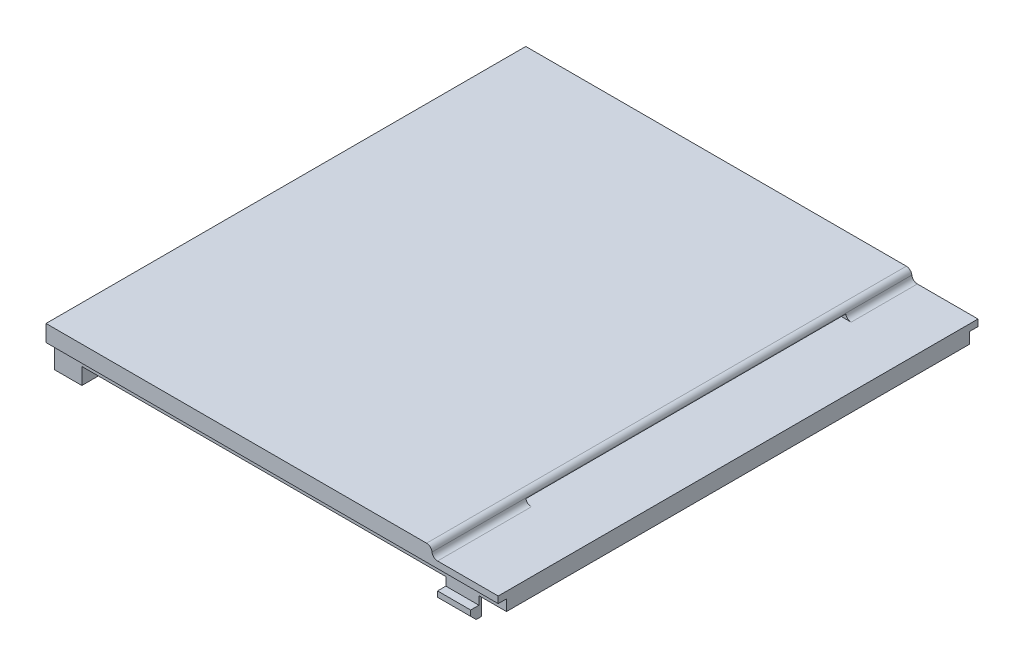
SolidWorks part; units mm, degrees
note: The reader was unsure of these and kept them because the rebuilt part matched: shared geometry of "Эскиз3<3>".
ref_plane "Front" through (0, 0, 0) normal (0, 0, 1) x (1, 0, 0)
ref_plane "Top" through (0, 0, 0) normal (0, 1, 0) x (1, 0, 0)
ref_plane "Right" through (0, 0, 0) normal (1, 0, 0) x (0, 0, -1)
sketch "Эскиз2" plane through (0, 0, 0) normal (1, 0, 0) x (0, 0, -1)
  line L0 (-42, -1.5) -> (-42, -3.5)
  line L1 (43.5, -1.5) -> (-43.5, -1.5)
  line L2 (43.5, -1.5) -> (43.5, 1.5)
  line L3 (43.5, 1.5) -> (-43.5, 1.5)
  line L4 (-43.5, -1.5) -> (-43.5, 1.5)
  line L5 (43.5, -1.5) -> (-43.5, 1.5) construction
  line L6 (43.5, 1.5) -> (-43.5, -1.5) construction
  line L7 (-42, -3.5) -> (-40, -3.5)
  line L8 (-40, -3.5) -> (-40, -1.5)
  line L9 (42, -1.5) -> (42, -3.5)
  line L10 (42, -3.5) -> (40, -3.5)
  line L11 (40, -3.5) -> (40, -1.5)
  line L12 (-40, -3.5) -> (40, -3.5)
  point P0 (0, 0)
  dimension "D1" = 3
  dimension "D2" = 87
  dimension "D3" = 2
  dimension "D4" = 2
  dimension "D5" = 2
  dimension "D6" = 2
  dimension "D7" = 84
  dimension "D8" = 42
extrude "Бобышка-Вытянуть1" add sketch "Эскиз2" along normal blind 82 contours L4 L1 L2 L3 | L7 L8 L1 L0 | L11 L10 L9 L1 | L8 L12 L11 L1
sketch "Эскиз3" plane through (0, 0, 0) normal (1, 0, 0) x (0, 0, -1)
  line L0 (-42, -6.5) -> (42, -6.5)
  line L1 (42, -6.5) -> (42, 1.5)
  line L2 (43.5, 1.5) -> (-43.5, 1.5) construction
  line L3 (42, 1.5) -> (-42, 1.5)
  line L4 (-42, 1.5) -> (-42, -6.5)
  line L6 (4.8, -4.65) -> (-4.8, -4.65)
  line L7 (4.8, -4.65) -> (4.8, -3.15)
  line L8 (4.8, -3.15) -> (-4.8, -3.15)
  line L9 (-4.8, -4.65) -> (-4.8, -3.15)
  line L10 (4.8, -4.65) -> (-4.8, -3.15) construction
  line L11 (4.8, -3.15) -> (-4.8, -4.65) construction
  line L12 (-25.2, -4.65) -> (-34.8, -4.65)
  line L13 (-25.2, -4.65) -> (-25.2, -3.15)
  line L14 (-25.2, -3.15) -> (-34.8, -3.15)
  line L15 (-34.8, -4.65) -> (-34.8, -3.15)
  line L16 (-25.2, -4.65) -> (-34.8, -3.15) construction
  line L17 (-25.2, -3.15) -> (-34.8, -4.65) construction
  line L18 (34.8, -4.65) -> (25.2, -4.65)
  line L19 (34.8, -4.65) -> (34.8, -3.15)
  line L20 (34.8, -3.15) -> (25.2, -3.15)
  line L21 (25.2, -4.65) -> (25.2, -3.15)
  line L22 (34.8, -4.65) -> (25.2, -3.15) construction
  line L23 (34.8, -3.15) -> (25.2, -4.65) construction
  point P4 (-30, -3.9)
  point P10 (0, -3.9)
  point P18 (30, -3.9)
  point P23 (0, 0)
  point P25 (0, 0)
  dimension "D1" = 8
  dimension "D2" = 30
  dimension "D3" = 30
  dimension "D4" = 1.5
  dimension "D5" = 9.6
  dimension "D6" = 9.6
  dimension "D7" = 9.6
  dimension "D8" = 1.5
  dimension "D9" = 1.5
  dimension "D10" = 3.9
extrude "Бобышка-Вытянуть2" add sketch "Эскиз3" along normal blind 5 contours L0 L1 L3 L4
extrude "Бобышка-Вытянуть3" add sketch "Эскиз3<3>" against normal blind 2 contours L21 L18 L19 L20 | L9 L6 L7 L8 | L15 L12 L13 L14
sketch "Эскиз3<3>" plane through (0, 0, 0) normal (1, 0, 0) x (0, 0, -1) same geometry as "Эскиз3"
sketch "Эскиз4" plane through (0, 0, 0) normal (1, 0, 0) x (0, 0, -1)
  line L1 (31.5, -0.3) -> (-26.5, -0.3)
  line L2 (31.5, -0.3) -> (31.5, 0.5)
  line L3 (31.5, 0.5) -> (-26.5, 0.5)
  line L4 (-26.5, -0.3) -> (-26.5, 0.5)
  line L5 (31.5, -0.3) -> (-26.5, 0.5) construction
  line L6 (31.5, 0.5) -> (-26.5, -0.3) construction
  point P0 (2.5, 0.1)
  dimension "D1" = 0.8
  dimension "D2" = 58
  dimension "D3" = 0.3
  dimension "D4" = 2.5
extrude "Вырез-Вытянуть1" cut sketch "Эскиз4" along normal through all
fillet "Скругление1" radius 1.2 1 edges at (0, -0.3, -2.5)
sketch "Эскиз5" plane through (0, 0, 0) normal (0, 1, 0) x (1, 0, 0)
  line L0 (0, 0) -> (70, 0)
  line L1 (70, 0) -> (70, 45.9648)
  line L2 (70, 45.9648) -> (87.6516, 45.9648)
  line L3 (87.6516, 45.9648) -> (87.6516, -47.5311)
  line L4 (87.6516, -47.5311) -> (70, -47.5311)
  line L5 (70, -47.5311) -> (70, 0)
  dimension "D1" = 70
extrude "Вырез-Вытянуть2" cut sketch "Эскиз5" along normal through all from surface at -0.3 contours L5 L4 L3 L2 L1 starting at face at (41.6, -0.3, -2.5)
sketch "Эскиз6" plane through (0, 0, 0) normal (1, 0, 0) x (0, 0, -1)
  line L0 (-42, -1.5) -> (-42, -3.5) construction
  line L1 (-42, -3.0496) -> (-42, -5)
  line L2 (-42, -5) -> (-43.5, -5)
  line L4 (-42, -7) -> (-41.5, -7)
  line L5 (-41.5, -7) -> (-41.5, -3.0496)
  line L6 (-42, -7) -> (-42.5, -7)
  line L7 (-42, -3.0496) -> (-41.5, -3.0496)
  line L8 (-42.5, -7) -> (-45.105, -4.395)
  line L9 (-43.5, -5) -> (-43.5, -6)
  dimension "D1" = 0.5
  dimension "D2" = 45
  dimension "D3" = 1.5
  dimension "D4" = 5.5
  dimension "D5" = 0.5
extrude "Бобышка-Вытянуть4" add sketch "Эскиз6" along normal blind 6 from offset 71 contours L2 L9 L8 L6 L4 L5 L7 L1
fillet "Скругление2" radius 1 1 edges at (70, -0.3, 35)
mirror "Зеркальное отражение1" about plane through (0, 0, 0) normal (0, 0, 1) of "Бобышка-Вытянуть4"
fillet "Скругление3" radius 1 1 edges at (70, 1.5, 0)
